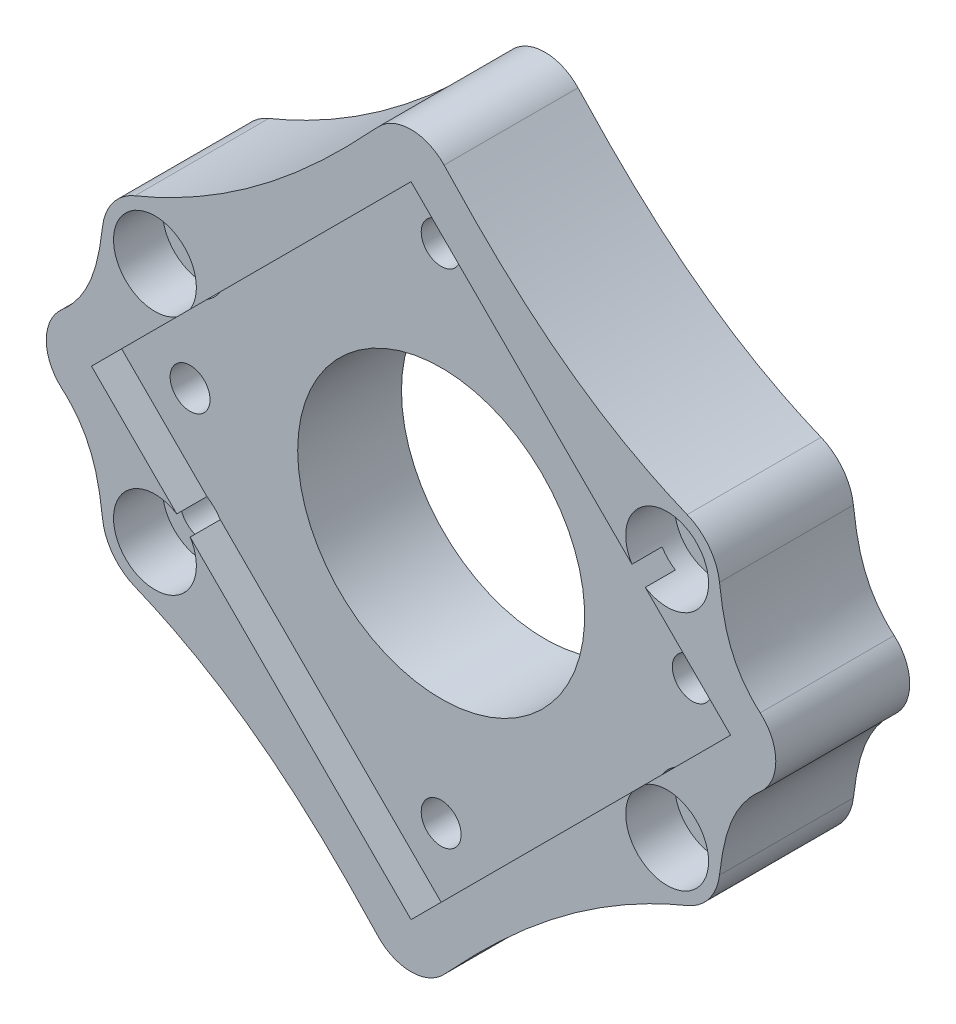
SolidWorks part; units mm, degrees
ref_plane "Front Plane" through (0, 0, 0) normal (0, 0, 1) x (1, 0, 0)
ref_plane "Top Plane" through (0, 0, 0) normal (0, 1, 0) x (1, 0, 0)
ref_plane "Right Plane" through (0, 0, 0) normal (1, 0, 0) x (0, 0, -1)
sketch "main_features_sketch" plane through (0, 0, 0) normal (0, 0, 1) x (1, 0, 0)
  line L0 (0, 42.4264) -> (42.4264, 0)
  line L1 (-13.4652, 36.8028) -> (3.5991, 55.0676) construction
  line L3 (-48.5848, 17.5752) -> (-24.5217, 27.4624) construction
  line L4 (-41.6186, 11.248) -> (-40.3262, 22.0483) construction
  line L5 (-50.1265, 1.2608) -> (-43.8642, 6.6974) construction
  line L7 (-34, 16) -> (34, 16) construction
  line L8 (-34, 16) -> (-34, -16) construction
  line L9 (-34, -16) -> (34, -16) construction
  line L10 (34, 16) -> (34, -16) construction
  line L11 (-34, 16) -> (34, -16) construction
  line L12 (-34, -16) -> (34, 16) construction
  line L13 (0, 42.4264) -> (-42.4264, 0)
  line L14 (42.4264, 0) -> (0, -42.4264)
  line L15 (-42.4264, 0) -> (0, -42.4264)
  line L16 (0, 42.4264) -> (0, -42.4264) construction
  line L17 (42.4264, 0) -> (-42.4264, 0) construction
  circle A0 centre (0, 0) radius 31
  circle A1 centre (0, 0) radius 25
  circle A2 centre (0, 0) radius 19.05
  circle A3 centre (0, 42.4264) radius 6
  circle A4 centre (42.4264, 0) radius 6
  circle A5 centre (0, -42.4264) radius 6
  circle A6 centre (-42.4264, 0) radius 6
  circle A7 centre (-34, 16) radius 7
  circle A8 centre (34, 16) radius 7
  circle A9 centre (34, -16) radius 7
  circle A10 centre (-34, -16) radius 7
  circle A11 centre (0, 0) radius 33.335 construction
  spline S0 degree 3 poles (-4.3843, 46.5225) (-11.4944, 38.9122) (-21.621, 28.6542) (-36.6604, 22.4747) knots 0 0 0 0 1 1 1 1
  spline S1 degree 3 poles (-40.9504, 16.8317) (-41.4889, 12.3316) (-42.3972, 7.971) (-46.3598, 4.5308) knots 0 0 0 0 1 1 1 1
  spline S2 degree 3 poles (40.9504, 16.8317) (41.4889, 12.3316) (42.3972, 7.971) (46.3598, 4.5308) knots 0 0 0 0 1 1 1 1
  spline S3 degree 3 poles (4.3843, 46.5225) (11.4944, 38.9122) (21.621, 28.6542) (36.6604, 22.4747) knots 0 0 0 0 1 1 1 1
  spline S4 degree 3 poles (-40.9504, -16.8317) (-41.4889, -12.3316) (-42.3972, -7.971) (-46.3598, -4.5308) knots 0 0 0 0 1 1 1 1
  spline S5 degree 3 poles (-4.3843, -46.5225) (-11.4944, -38.9122) (-21.621, -28.6542) (-36.6604, -22.4747) knots 0 0 0 0 1 1 1 1
  spline S6 degree 3 poles (40.9504, -16.8317) (41.4889, -12.3316) (42.3972, -7.971) (46.3598, -4.5308) knots 0 0 0 0 1 1 1 1
  spline S7 degree 3 poles (4.3843, -46.5225) (11.4944, -38.9122) (21.621, -28.6542) (36.6604, -22.4747) knots 0 0 0 0 1 1 1 1
  point P32 (0, 0)
  dimension "D2" = 62
  dimension "D3" = 50
  dimension "D4" = 38.1
  dimension "D1" = 66.67
  dimension "D8" = 12
  dimension "D9" = 14
  dimension "D5" = 32
  dimension "D6" = 68
  dimension "D7" = 60
extrude "main_body" add sketch "main_features_sketch" along normal blind 17.78 contours A3 S0 A7 L13 A0 | L13 A7 | A7 S1 A6 L13 | L13 A6 L15 | L13 A7 A0 | A10 A0 A7 L13 A6 L15 | L15 A6 L13 | A7 A0 L13 | L13 A0 | L0 A3 L13 | L13 A3 L0 | A3 L13 A0 L0 | S3 A3 L0 A0 A8 | L0 A0 | L0 A8 | L0 A8 A0 | A0 A8 | S2 A8 L0 A4 | A9 L14 A4 L0 A8 A0 | L14 A4 L0 | L0 A4 L14 | A9 S6 A4 L14 | L14 A9 | L14 A9 A0 | A0 A9 | A9 A0 L14 | A5 S7 A9 L14 A0 | L14 A0 | A5 L14 A0 L15 | L14 A5 L15 | L15 A5 L14 | S5 A5 L15 A0 A10 | L15 A0 | L15 A10 | L15 A10 A0 | A0 A10 | A10 L15 A0 | S4 A10 L15 A6 | A10 A0 L15 L14 A9 A8 L0 L13 A7 A1 | A1 A2 | A0 A7 | A8 L0 A0 region at (0, 43.6268, 0) region at (0, 38.8251, 0) region at (18.2638, 29.7353, 0) region at (0, 32.9403, 0) region at (-18.2638, 29.7353, 0) region at (21.4964, 21.4964, 0) region at (20.5932, 20.5932, 0) region at (-21.4964, 21.4964, 0) region at (26.9386, 15.41, 0) region at (-26.9386, 15.41, 0) region at (-34.3003, 16.3003, 0) region at (34.3003, 16.3003, 0) region at (30.0007, 11.5522, 0) region at (27.882, 13.1209, 0) region at (-30.0007, 11.5522, 0) region at (-27.882, 13.1209, 0) region at (-39.6396, 8.4347, 0) region at (39.6396, 8.4347, 0) region at (33.4223, 0, 0) region at (-33.4223, 0, 0) region at (-43.6268, 0, 0) region at (43.6268, 0, 0) region at (38.8251, 0, 0) region at (-38.8251, 0, 0) region at (-27.882, -13.1209, 0) region at (-30.0007, -11.5522, 0) region at (-39.6396, -8.4347, 0) region at (39.6396, -8.4347, 0) region at (30.0007, -11.5522, 0) region at (27.882, -13.1209, 0) region at (-26.9386, -15.41, 0) region at (-34.3003, -16.3003, 0) region at (34.3003, -16.3003, 0) region at (26.9386, -15.41, 0) region at (-18.2638, -29.7353, 0) region at (-21.4964, -21.4964, 0) region at (18.2638, -29.7353, 0) region at (21.4964, -21.4964, 0) region at (0, -32.9403, 0) region at (0, -43.6268, 0) region at (0, -38.8251, 0) region at (-24.2929, 0, 0)
extrude "ring_pocket" cut sketch "Sketch1<8>" along normal blind 2 contours A10 A0 L15 L14 A9 A8 L0 L13 A7 A1 | A0 A7 | L13 A0 | L0 A0 | A0 A8 | A0 A9 | L14 A0 | L15 A0 | A0 A10 region at (21.4964, 21.4964, 0) region at (20.5932, 20.5932, 0) region at (-21.4964, 21.4964, 0) region at (27.882, 13.1209, 0) region at (-27.882, 13.1209, 0) region at (-27.882, -13.1209, 0) region at (27.882, -13.1209, 0) region at (-21.4964, -21.4964, 0) region at (21.4964, -21.4964, 0)
sketch "Sketch1<8>" plane through (0, 0, 0) normal (0, 0, 1) x (1, 0, 0) same geometry as "main_features_sketch"
hole_wizard "CBORE for M6 SHCS1" positions "Sketch2" profile "Sketch3" counterbore size "M6" standard "ANSI Metric" end condition through all
sketch "Sketch2" plane through (0, 0, 17.78) normal (0, 0, 1) x (1, 0, 0)
  point P0 (-34, 16)
  point P3 (-34, -16)
  point P6 (34, -16)
  point P9 (34, 16)
sketch "Sketch3" plane through (-34, 16, 17.78) normal (1, 0, 0) x (0, -1, 0)
  line L0 (0, 0) -> (0, 17.78)
  line L1 (0, 17.78) -> (3.2, 17.78)
  line L3 (3.2, 17.78) -> (3.2, 6.5)
  line L4 (3.2, 6.5) -> (5.5, 6.5)
  line L5 (5.5, 6.5) -> (5.5, 0)
  line L7 (5.5, 0) -> (0, 0)
  line L11 (0, -6.35) -> (0, 107.95) construction
  dimension "Thru Hole Dia." = 6.4
  dimension "Thru Hole Depth" = 17.78
  dimension "C'Bore Dia." = 11
  dimension "C'Bore Depth" = 6.5
hole_wizard "CBORE for M5 SHCS1" positions "Sketch4" profile "Sketch5" counterbore size "M5" standard "ANSI Metric" end condition through all
sketch "Sketch4" plane through (0, 0, 0) normal (0, 0, -1) x (-1, 0, 0)
  line L0 (0, 42.4264) -> (0, -42.4264) construction
  line L1 (-42.4264, 0) -> (42.4264, 0) construction
  circle A0 centre (0, 0) radius 33.335 construction
  point P17 (0, 33.335)
  point P23 (33.335, 0)
  point P27 (0, -33.335)
  point P29 (-33.335, 0)
sketch "Sketch5" plane through (0, 33.335, 0) normal (1, 0, 0) x (0, 1, 0)
  line L0 (0, 0) -> (0, 17.78)
  line L1 (0, 17.78) -> (2.65, 17.78)
  line L3 (2.65, 17.78) -> (2.65, 5.5)
  line L4 (2.65, 5.5) -> (5, 5.5)
  line L5 (5, 5.5) -> (5, 0)
  line L7 (5, 0) -> (0, 0)
  line L11 (0, -6.35) -> (0, 107.95) construction
  dimension "Thru Hole Dia." = 5.3
  dimension "Thru Hole Depth" = 17.78
  dimension "C'Bore Dia." = 10
  dimension "C'Bore Depth" = 5.5
extrude "Cut-Extrude5" cut sketch "main_features_sketch<9>" against normal blind 4 from surface contours L13 L15 L14 L0 starting at face at (-2.65, 33.335, 17.78)
sketch "main_features_sketch<9>" plane through (0, 0, 0) normal (0, 0, 1) x (1, 0, 0) same geometry as "main_features_sketch"
